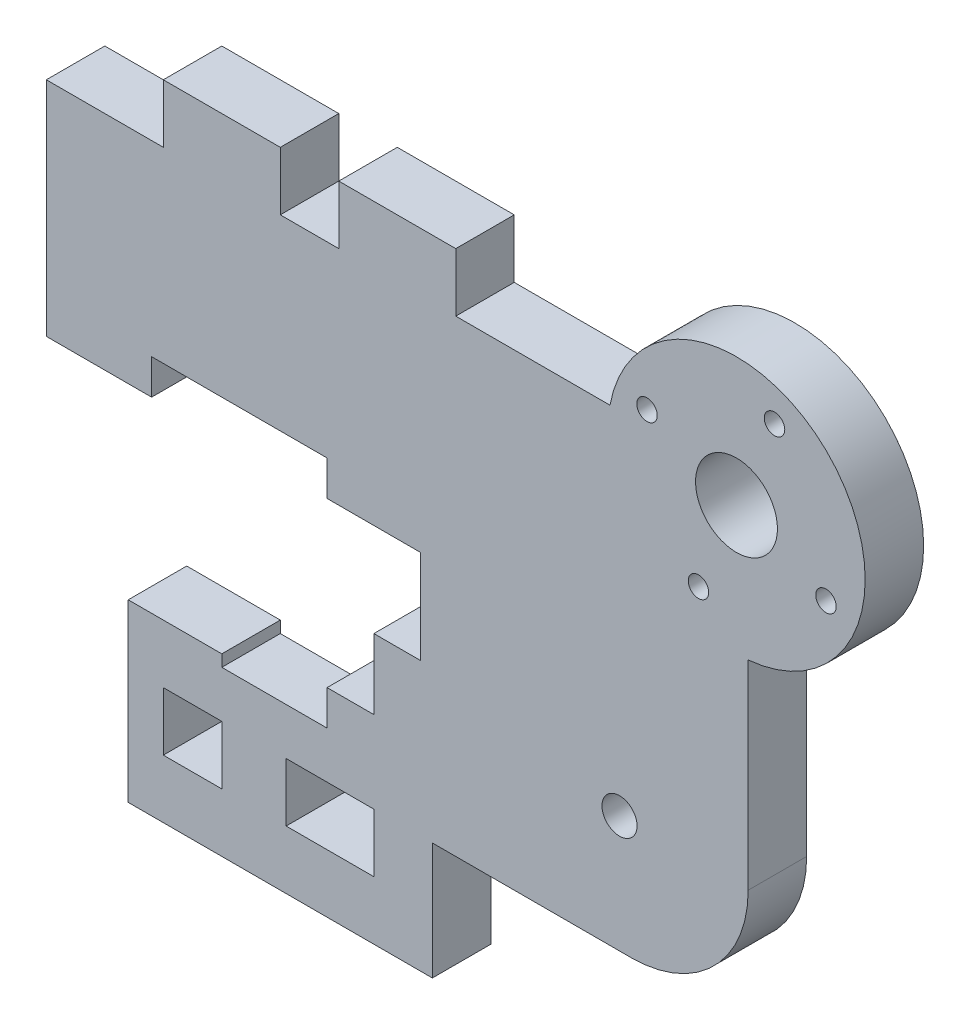
SolidWorks part; units mm, degrees
ref_plane "Plan de face" through (0, 0, 0) normal (0, 0, 1) x (1, 0, 0)
ref_plane "Plan de dessus" through (0, 0, 0) normal (0, 1, 0) x (1, 0, 0)
ref_plane "Plan de droite" through (0, 0, 0) normal (1, 0, 0) x (0, 0, -1)
sketch "Esquisse1" plane through (0, 0, 0) normal (0, 0, 1) x (1, 0, 0)
  line L0 (-8, -10) -> (18, -10)
  line L1 (18, 0) -> (18, -10)
  line L2 (0, 5) -> (0, 4)
  line L3 (5, 40) -> (10, 40)
  line L4 (40.75, 30.35) -> (47.25, 45.65) construction
  line L5 (20, 40) -> (33.1833, 40)
  line L6 (-5, 40) -> (-5, 45)
  line L7 (-5, 45) -> (5, 45)
  line L8 (5, 40) -> (5, 45)
  line L9 (18, 0) -> (45, 0)
  line L10 (10, 40) -> (10, 45)
  line L11 (10, 45) -> (20, 45)
  line L12 (20, 40) -> (20, 45)
  line L14 (13, 0) -> (5.5, 0)
  line L15 (13, 0) -> (13, -5)
  line L16 (13, -5) -> (5.5, -5)
  line L17 (5.5, 0) -> (5.5, -5)
  line L18 (0, 0) -> (-5, 0)
  line L19 (-6, 21) -> (-6, 24)
  line L20 (0, 4) -> (9, 4)
  line L21 (44, 38) -> (36.35, 38) construction
  line L22 (-6, 24) -> (9, 24)
  line L23 (17, 13) -> (17, 21)
  line L24 (0, 0) -> (0, -5)
  line L25 (0, 0) -> (0, 5)
  line L26 (0, 5) -> (-8, 5)
  line L27 (-8, -10) -> (-8, 5)
  line L28 (-5, 40) -> (-15, 40)
  line L29 (0, -5) -> (-5, -5)
  line L30 (-6, 21) -> (-15, 21)
  line L31 (-15, 40) -> (-15, 21)
  line L32 (17, 21) -> (9, 21)
  line L33 (36.35, 38) -> (36.35, 41.25) construction
  line L34 (9, 7) -> (13, 7)
  line L35 (9, 21) -> (9, 24)
  line L36 (17, 13) -> (13, 13)
  line L37 (51.65, 34.75) -> (36.35, 41.25) construction
  line L38 (45, 0) -> (45, 27.0455)
  line L39 (9, 7) -> (9, 4)
  line L40 (-5, 0) -> (-5, -5)
  line L41 (13, 7) -> (13, 13)
  circle A0 centre (34, 10) radius 1.5
  circle A1 centre (44, 38) radius 3.5
  arc A2 (45, 27.0455) -> (33.1833, 40) centre (44, 38) ccw
  circle A3 centre (36.35, 38) radius 0.875 construction
  circle A4 centre (36.35, 41.25) radius 0.875
  circle A5 centre (47.25, 45.65) radius 0.875
  circle A6 centre (51.65, 34.75) radius 0.875
  circle A7 centre (40.75, 30.35) radius 0.875
  point P38 (0, 0)
  point P56 (44, 38)
  dimension "D18" = 45
  dimension "D19" = 3
  dimension "D25" = 3.25
  dimension "D27" = 11
  dimension "D28" = 1.75
  dimension "D24" = 7
  dimension "D3" = 10
  dimension "D4" = 5
  dimension "D5" = 5
  dimension "D6" = 8
  dimension "D7" = 15
  dimension "D8" = 10
  dimension "D9" = 19
  dimension "D10" = 3
  dimension "D11" = 9
  dimension "D12" = 4
  dimension "D13" = 11
  dimension "D14" = 3
  dimension "D15" = 8
  dimension "D16" = 8
  dimension "D17" = 8
  dimension "D20" = 28
  dimension "D21" = 10
  dimension "D22" = 17
  dimension "D23" = 10
  dimension "D26" = 7.65
  dimension "D30" = 4
  dimension "D31" = 3
  dimension "D32" = 1
  dimension "D33" = 15
  dimension "D34" = 40
  dimension "D35" = 26
  dimension "D36" = 5
  dimension "D37" = 5
  dimension "D38" = 7.5
  dimension "D39" = 5
  dimension "D29" = 4
extrude "Boss.-Extru.1" add sketch "Esquisse1" along normal blind 5 contours L5 L12 L11 L10 L3 L8 L7 L6 | L28 L31 L30 | L19 L22 L23 L20 L2 L25 L9 | L27 L25 L26 region at (20.2981, 22.1895, 0)
fillet "Congé1" radius 10 1 edges at (45, 0, 2.5)
